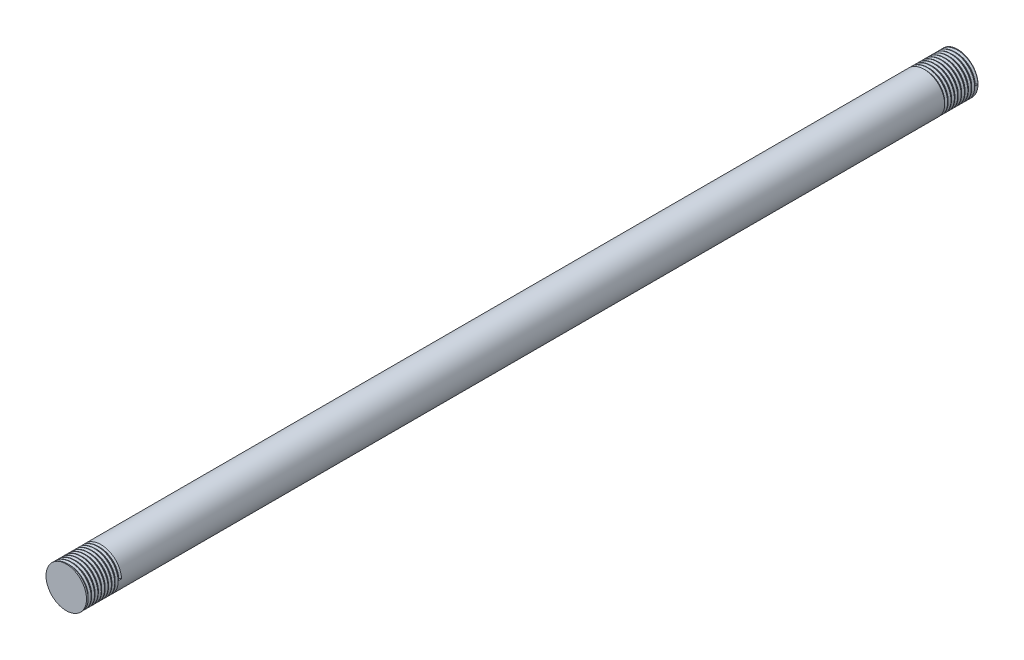
SolidWorks part; units mm, degrees
ref_plane "Front Plane" through (0, 0, 0) normal (0, 0, 1) x (1, 0, 0)
ref_plane "Top Plane" through (0, 0, 0) normal (0, 1, 0) x (1, 0, 0)
ref_plane "Right Plane" through (0, 0, 0) normal (1, 0, 0) x (0, 0, -1)
sketch "Sketch1" plane through (0, 0, 0) normal (0, 0, 1) x (1, 0, 0)
  circle A0 centre (0, 0) radius 7.5
  dimension "D1" = 15
extrude "Boss-Extrude1" add sketch "Sketch1" along normal blind 330.2
thread "Thread4" pitch 1.25 method cut profile "Thread Profile4" start angle 0, offset 0, length 0, pitch 1.25, diameter 15
ref_plane "Plane6" through (7.5, 0, 0) normal (0, -1, 0) x (1, 0, 0)
sketch "Thread Profile4" plane through (7.5, 0, 0) normal (0, -1, 0) x (1, 0, 0)
  line L0 (0, 0) -> (0, 1.25) construction
  line L11 (0, 0) -> (0, 1.0937)
  line L12 (0, 1.0937) -> (-0.6766, 0.7031)
  line L13 (-0.6766, 0.7031) -> (-0.6766, 0.3906)
  line L15 (-0.6766, 0.3906) -> (0, 0)
  line L17 (-0.6766, 0.5469) -> (0, 0.5469) construction
  point P2 (0, 0)
  dimension "Pitch" = 1.25
  dimension "Profile_Angle" = 60
  dimension "Profile_Land" = 0.3125
  dimension "Profile_Height" = 0.6766
thread "Thread5" pitch 1.25 method cut profile "Thread Profile5" start angle 0, offset 0, length 0, pitch 1.25, diameter 15
ref_plane "Plane7" through (-7.5, 0, 330.2) normal (0, -1, 0) x (-1, 0, 0)
sketch "Thread Profile5" plane through (-7.5, 0, 330.2) normal (0, -1, 0) x (-1, 0, 0)
  line L0 (0, 0) -> (0, 1.25) construction
  line L11 (0, 0) -> (0, 1.0937)
  line L12 (0, 1.0937) -> (-0.6766, 0.7031)
  line L13 (-0.6766, 0.7031) -> (-0.6766, 0.3906)
  line L15 (-0.6766, 0.3906) -> (0, 0)
  line L17 (-0.6766, 0.5469) -> (0, 0.5469) construction
  point P2 (0, 0)
  dimension "Pitch" = 1.25
  dimension "Profile_Angle" = 60
  dimension "Profile_Land" = 0.3125
  dimension "Profile_Height" = 0.6766
